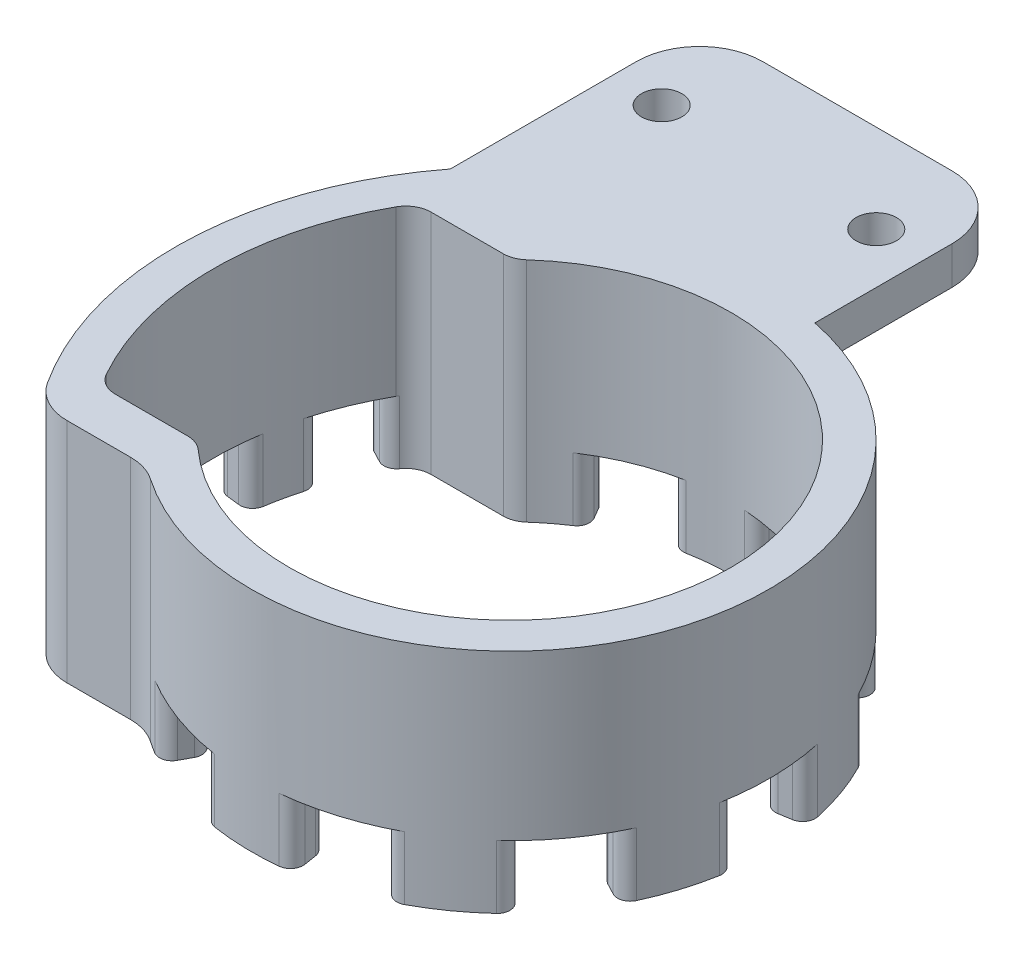
SolidWorks part; units mm, degrees
ref_plane "Front Plane" through (0, 0, 0) normal (0, 0, 1) x (1, 0, 0)
ref_plane "Top Plane" through (0, 0, 0) normal (0, 1, 0) x (1, 0, 0)
ref_plane "Right Plane" through (0, 0, 0) normal (1, 0, 0) x (0, 0, -1)
sketch "Sketch1" plane through (0, 0, 0) normal (0, 1, 0) x (1, 0, 0)
  line L0 (-12.2474, 12.5) -> (-19.8997, 12.5)
  line L1 (-20.9567, 16.2194) -> (-12.5372, 16.2194)
  line L2 (-19.8997, -12.5) -> (-12.2474, -12.5)
  line L7 (-12.5372, -16.2194) -> (-20.9567, -16.2194)
  arc A0 (-12.2474, -12.5) -> (-12.2474, 12.5) centre (0, 0) ccw
  arc A1 (-19.8997, 12.5) -> (-19.8997, -12.5) centre (0, 0) ccw
  arc A2 (-20.9567, 16.2194) -> (-20.9567, -16.2194) centre (0, 0) ccw
  arc A4 (-12.5372, -16.2194) -> (-12.5372, 16.2194) centre (0, 0) ccw
  point P1 (-23.5, 0)
  point P3 (17.5, 0)
  dimension "D1" = 35
  dimension "D9" = 3
  dimension "D2" = 41
  dimension "D3" = 25
extrude "Boss-Extrude1" add sketch "Sketch1" along normal blind 18
sketch "Sketch2" plane through (0, 18, 0) normal (0, 1, 0) x (1, 0, 0)
  line L0 (-20.9567, 16.2194) -> (-20.9567, 35.9613)
  line L1 (-20.9567, 35.9613) -> (4.0433, 35.9613)
  line L2 (4.0433, 35.9613) -> (4.0433, 20.0973)
  line L3 (-12.5372, 16.2194) -> (-20.9567, 16.2194) construction
  line L4 (-12.5372, 16.2194) -> (-20.9567, 16.2194)
  arc A0 (-12.5372, -16.2194) -> (-12.5372, 16.2194) centre (0, 0) ccw construction
  arc A1 (4.0433, 20.0973) -> (-12.5372, 16.2194) centre (0, 0) ccw
  point P3 (-4.6687, 19.9613)
  dimension "D1" = 16
  dimension "D2" = 25
extrude "Boss-Extrude2" add sketch "Sketch2" against normal blind 3
sketch "Sketch3" plane through (0, 18, 0) normal (0, 1, 0) x (1, 0, 0)
  line L0 (-20.9567, 35.9613) -> (-20.9567, 16.2194) construction
  line L1 (4.0433, 20.0973) -> (4.0433, 35.9613) construction
  line L2 (4.0433, 35.9613) -> (-20.9567, 35.9613) construction
  circle A0 centre (-16.9567, 28.9613) radius 1.6
  circle A1 centre (0.0433, 28.9613) radius 1.6
  dimension "D3" = 3.2
  dimension "D1" = 4
  dimension "D2" = 4
  dimension "D4" = 7
extrude "Cut-Extrude1" cut sketch "Sketch3" against normal through all
fillet "Fillet1" radius 2 4 edges at (-12.2474, 9, 12.5) (-19.8997, 9, 12.5) (-19.8997, 9, -12.5) (-12.2474, 9, -12.5)
fillet "Fillet2" radius 4 4 edges at (-20.9567, 9, 16.2194) (-12.5372, 9, 16.2194) (-20.9567, 7.5, -16.2194) (-12.5372, 7.5, -16.2194)
fillet "Fillet3" radius 2 4 edges at (-20.8047, 15, -15.7328) (-16.3643, 15, -16.2194) (-12.6535, 15, -16.3981) (-4.0884, 15, -20.0882)
fillet "Fillet4" radius 5 2 edges at (-20.9567, 16.5, -35.9613) (4.0433, 16.5, -35.9613)
sketch "Sketch4" plane through (0, 0, 0) normal (0, -1, 0) x (1, 0, 0)
  line L2 (-13.8357, 16.2194) -> (-18.8928, 16.2194)
  line L3 (-18.8928, -16.2194) -> (-13.8357, -16.2194)
  line L8 (-10.3274, -17.7086) -> (-8.8161, -15.1171)
  line L9 (-4.8982, -19.9062) -> (-4.1814, -16.9931)
  arc A5 (-11.7011, -13.0128) -> (-11.7011, 13.0128) centre (0, 0) ccw construction
  arc A6 (-18.8928, 16.2194) -> (-22.2515, 14.3917) centre (-18.8928, 12.2194) ccw
  arc A7 (-22.2515, 14.3917) -> (-22.2515, -14.3917) centre (0, 0) ccw
  arc A8 (-22.2515, -14.3917) -> (-18.8928, -16.2194) centre (-18.8928, -12.2194) ccw
  arc A9 (-11.5768, -16.9182) -> (-13.8357, -16.2194) centre (-13.8357, -20.2194) ccw
  arc A10 (-11.5768, -16.9182) -> (-11.5768, 16.9182) centre (0, 0) ccw
  arc A11 (-13.8357, 16.2194) -> (-11.5768, 16.9182) centre (-13.8357, 20.2194) ccw
  arc A16 (-10.3274, -17.7086) -> (-4.8982, -19.9062) centre (0, 0) ccw
  arc A23 (-8.8161, -15.1171) -> (-4.1814, -16.9931) centre (0, 0) ccw
  dimension "D2" = 5
  dimension "D1" = 0
extrude "Cut-Extrude2" cut sketch "Sketch4" against normal blind 5
ref_axis "Axis1" through (0, -0.9, 0) along (0, 1, 0)
fillet "Fillet5" radius 1 4 edges at (-4.8982, 2.5, -19.9062) (-10.3274, 2.5, -17.7086) (-8.8161, 2.5, -15.1171) (-4.1814, 2.5, -16.9931)
pattern_circular "CirPattern1" count 7 every 37 about axis through (0, -0.9, 0) along (0, 1, 0) of "Cut-Extrude2", "Fillet5" reverse direction yes
sketch "Sketch5" plane through (0, 0, 0) normal (0, -1, 0) x (1, 0, 0)
  line L0 (-20.8243, -10.8903) -> (-23.4827, -12.2805)
  line L1 (-22.3696, -7.2008) -> (-25.2253, -8.1201)
  arc A0 (-22.2515, 14.3917) -> (-22.2515, -14.3917) centre (0, 0) ccw construction
  arc A1 (-20.5069, 11.4767) -> (-20.5069, -11.4767) centre (0, 0) ccw construction
  arc A2 (-25.2253, -8.1201) -> (-23.4827, -12.2805) centre (0, 0) ccw
  arc A3 (-22.3696, -7.2008) -> (-20.8243, -10.8903) centre (0, 0) ccw
  dimension "D1" = 4
extrude "Cut-Extrude3" cut sketch "Sketch5" against normal blind 5
fillet "Fillet6" radius 1 4 edges at (-25.2253, 2.5, -8.1201) (-22.3696, 2.5, -7.2008) (-23.4827, 2.5, -12.2805) (-20.8243, 2.5, -10.8903)
pattern_circular "CirPattern2" count 3 every 21 about axis through (0, -0.9, 0) along (0, 1, 0) of "Cut-Extrude3", "Fillet6"
